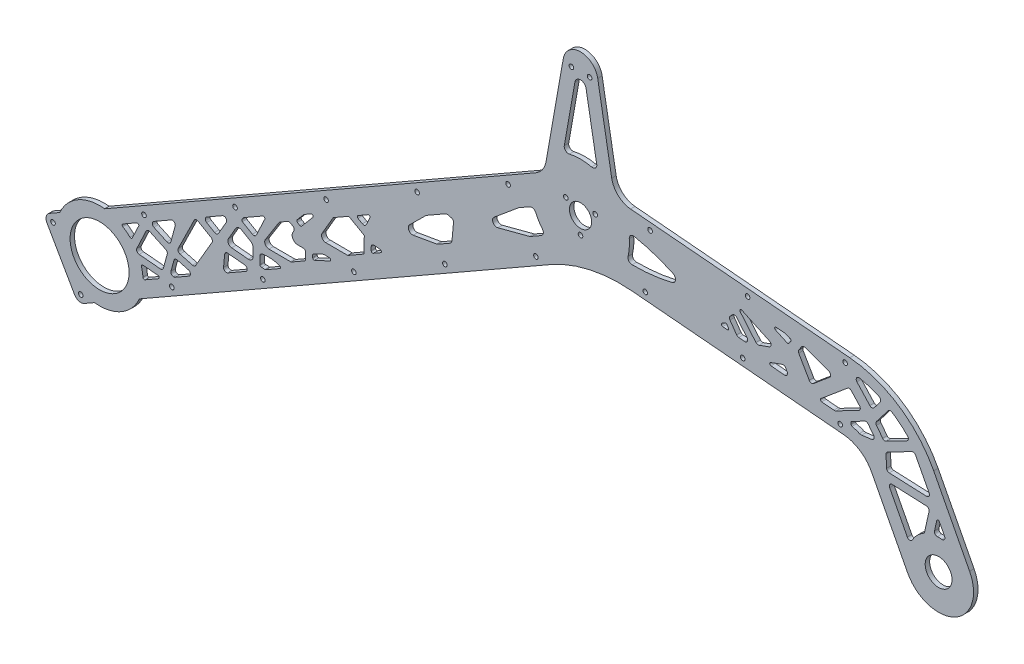
SolidWorks part; units mm, degrees
material "6061-T6 (SS)"
ref_plane "Front Plane" through (0, 0, 0) normal (0, 0, 1) x (1, 0, 0)
ref_plane "Top Plane" through (0, 0, 0) normal (0, 1, 0) x (1, 0, 0)
ref_plane "Right Plane" through (0, 0, 0) normal (1, 0, 0) x (0, 0, -1)
sketch "Reference Sketch" plane through (0, 0, 0) normal (0, 0, 1) x (1, 0, 0)
  line L0 (-343.92, -196.825) -> (0, 0) construction
  line L1 (-243.92, 103.175) -> (356.08, 103.175) construction
  line L2 (-243.92, 103.175) -> (-243.92, 0) construction
  line L3 (-243.92, 0) -> (356.08, 0) construction
  line L4 (356.08, 103.175) -> (356.08, 0) construction
  line L5 (0, 0) -> (256.08, -92.7116) construction
  line L6 (256.08, -92.7116) -> (56.08, -196.825) construction
  line L7 (256.08, -92.7116) -> (456.08, -196.825) construction
  line L8 (-343.92, -196.825) -> (56.08, -196.825) construction
  line L9 (56.08, -196.825) -> (456.08, -196.825) construction
  circle A1 centre (-343.92, -196.825) radius 100 construction
  circle A2 centre (56.08, -196.825) radius 100 construction
  circle A3 centre (456.08, -196.825) radius 100 construction
  circle A4 centre (-343.92, -196.825) radius 16.05 construction
  circle A5 centre (-343.92, -196.825) radius 28.55 construction
  circle A6 centre (-343.92, -196.825) radius 38.55 construction
  circle A7 centre (-343.92, -196.825) radius 33.55 construction
  point P13 (-343.92, -296.825)
  point P14 (556.08, -196.825)
  point P17 (-443.92, -196.825)
  dimension "D3" = 32.1
  dimension "D5" = 200
  dimension "D9" = 57.1
  dimension "D10" = 10
  dimension "D11" = 5
  dimension "D1" = 600
  dimension "D2" = 103.175
  dimension "D4" = 243.92
  dimension "D6" = 125
  dimension "D7" = 400
  dimension "D8" = 1000
sketch "Sketch2" plane through (0, 0, 0) normal (0, 0, 1) x (1, 0, 0)
  line L0 (-379.7168, -188.5069) -> (-32.0065, 10.4873)
  line L1 (-354.8814, -231.9028) -> (-21.5627, -41.1449)
  line L2 (-343.92, -196.825) -> (0, 0) construction
  line L3 (-184.3777, -76.7146) -> (-159.5423, -120.1104) construction
  line L4 (-24.685, 20.9013) -> (-12.3101, 91.0831)
  line L5 (12.3101, 91.0831) -> (22.322, 34.3028)
  line L6 (0, 98.4125) -> (0, 112.7) construction
  line L7 (-5.4848, 79.4125) -> (5.4848, 79.4125) construction
  line L8 (5.4848, 79.4125) -> (10.9697, 88.9125) construction
  line L9 (10.9697, 88.9125) -> (5.4848, 98.4125) construction
  line L10 (5.4848, 98.4125) -> (-5.4848, 98.4125) construction
  line L11 (-5.4848, 98.4125) -> (-10.9697, 88.9125) construction
  line L12 (-10.9697, 88.9125) -> (-5.4848, 79.4125) construction
  line L13 (-243.92, 103.175) -> (356.08, 103.175) construction
  line L14 (0, 88.9125) -> (0, 0) construction
  line L15 (35.7868, 21.9646) -> (192.5861, 8.2464)
  line L16 (252.5753, -31.8371) -> (278.2553, -81.1679)
  line L17 (233.9047, -104.2553) -> (208.2247, -54.9245)
  line L18 (36.8237, -28.3172) -> (188.2284, -41.5633)
  line L19 (0, 0) -> (192.5861, -16.8491) construction
  line L21 (-365.6311, -190.9191) -> (-338.0141, -175.1139) construction
  line L22 (-381.5729, -195.33) -> (-361.7045, -230.0467)
  line L23 (256.08, -92.7116) -> (56.08, -196.825) construction
  line L25 (-243.92, 0) -> (356.08, 0) construction
  circle A0 centre (0, 0) radius 7.9375
  circle A1 centre (-343.92, -196.825) radius 16.05
  arc A3 (-12.3101, 91.0831) -> (12.3101, 91.0831) centre (0, 88.9125) cw
  circle A4 centre (0, 88.9125) radius 6.5 construction
  circle A5 centre (-6.5, 88.9125) radius 1.65
  circle A6 centre (6.5, 88.9125) radius 1.65
  circle A7 centre (0, 88.9125) radius 9.5 construction
  arc A8 (252.5753, -31.8371) -> (192.5861, 8.2464) centre (186.0495, -66.4682) ccw
  circle A9 centre (256.08, -92.7116) radius 9.5885
  arc A10 (278.2553, -81.1679) -> (233.9047, -104.2553) centre (256.08, -92.7116) cw
  arc A11 (-21.5627, -41.1449) -> (36.8237, -28.3172) centre (28.1082, -127.9366) cw
  arc A12 (188.2284, -41.5633) -> (208.2247, -54.9245) centre (186.0495, -66.4682) cw
  arc A13 (22.322, 34.3028) -> (35.7868, 21.9646) centre (37.0941, 36.9075) ccw
  arc A14 (-32.0065, 10.4873) -> (-24.685, 20.9013) centre (-39.4572, 23.506) ccw
  circle A17 centre (-343.92, -196.825) radius 22.5 construction
  circle A18 centre (-365.6311, -190.9191) radius 1.65
  circle A19 centre (-338.0141, -175.1139) radius 1.65
  circle A20 centre (-322.2089, -202.7309) radius 1.65
  circle A21 centre (-349.8259, -218.5361) radius 1.65
  arc A27 (-379.7168, -188.5069) -> (-381.5729, -195.33) centre (-377.2333, -192.8465) ccw
  arc A28 (-361.7045, -230.0467) -> (-354.8814, -231.9028) centre (-357.3649, -227.5632) ccw
  circle A29 centre (-343.92, -196.825) radius 33.55 construction
  circle A32 centre (-343.92, -196.825) radius 38.55 construction
  point P16 (-171.96, -98.4125)
  point P64 (-343.92, -196.825)
  dimension "D1" = 15.875
  dimension "D2" = 32.1
  dimension "D3" = 45
  dimension "D5" = 13
  dimension "D6" = 3.3
  dimension "D7" = 6
  dimension "D12" = 50
  dimension "D14" = 100
  dimension "D16" = 15
  dimension "D17" = 5
  dimension "D18" = 25
  dimension "D19" = 3.3
  dimension "D15" = 4
  dimension "D20" = 19.177
  dimension "D4" = 50
  dimension "D8" = 19
  dimension "D9" = 14.2875
  dimension "D10" = 9.525
  dimension "D11" = 10
  dimension "D13" = 50
extrude "Base" add sketch "Sketch2" along normal blind 3.175
sketch "Sketch3" plane through (0, 0, 3.175) normal (0, 0, 1) x (1, 0, 0)
  line L0 (-343.92, -196.825) -> (0, 0) construction
  line L5 (0, 0) -> (197.3986, -17.2701) construction
  line L6 (192.5861, 8.2464) -> (35.7868, 21.9646) construction
  line L9 (36.8237, -28.3172) -> (188.2284, -41.5633) construction
  line L10 (-31.8958, -41.2976) -> (0, 0) construction
  line L11 (0, 0) -> (46.2693, -24.1244) construction
  circle A0 centre (-357.3649, -227.5632) radius 1.65
  circle A1 centre (-343.92, -196.825) radius 33.55 construction
  arc A2 (-361.7045, -230.0467) -> (-354.8814, -231.9028) centre (-357.3649, -227.5632) ccw construction
  circle A3 centre (-292.2711, -190.3101) radius 1.65
  circle A4 centre (-227.1773, -153.057) radius 1.65
  circle A5 centre (-162.0835, -115.8038) radius 1.65
  circle A6 centre (-96.9897, -78.5507) radius 1.65
  circle A7 centre (-31.8958, -41.2976) radius 1.65
  circle A8 centre (-312.1394, -155.5934) radius 1.65
  circle A9 centre (-377.2333, -192.8465) radius 1.65
  circle A10 centre (-247.0456, -118.3403) radius 1.65
  circle A11 centre (-181.9518, -81.0871) radius 1.65
  circle A12 centre (-116.858, -43.834) radius 1.65
  circle A13 centre (-51.7642, -6.5809) radius 1.65
  circle A14 centre (46.2693, -24.1244) radius 1.65
  circle A15 centre (116.0029, -30.2253) radius 1.65
  circle A16 centre (185.7366, -36.3262) radius 1.65
  circle A17 centre (189.2228, 3.5215) radius 1.65
  circle A18 centre (119.4892, 9.6224) radius 1.65
  circle A19 centre (49.7555, 15.7234) radius 1.65
  dimension "D1" = 3.3
  dimension "D2" = 6
  dimension "D3" = 5
  dimension "D5" = 3
  dimension "D4" = 75
  dimension "D6" = 70
extrude "Strut Holes" cut sketch "Sketch3" against normal through all
sketch "Sketch6" plane through (0, 0, 3.175) normal (0, 0, 1) x (1, 0, 0)
  line L0 (-315.2692, -197.7109) -> (-301.7593, -189.9792)
  line L1 (-354.8814, -231.9028) -> (-21.5627, -41.1449) construction
  line L2 (-289.845, -183.1607) -> (-279.9388, -177.4914)
  line L3 (-225.0683, -146.089) -> (-215.0659, -140.3647)
  line L4 (-202.4189, -105.5114) -> (-200.6862, -106.5205)
  line L5 (-330.4255, -170.6672) -> (-317.3783, -163.2003)
  line L6 (-32.0065, 10.4873) -> (-379.7168, -188.5069) construction
  line L7 (-315.9769, -164.4942) -> (-323.4022, -180.2613)
  line L8 (-325.3934, -181.4009) -> (-327.8261, -181.1787)
  line L9 (-302.165, -188.1154) -> (-317.5291, -186.7124)
  line L10 (-319.5204, -187.852) -> (-321.9207, -192.9489)
  line L11 (-295.5333, -171.6316) -> (-298.2962, -181.7883)
  line L12 (-300.4079, -183.2551) -> (-315.6625, -181.8621)
  line L13 (-317.2901, -179.0183) -> (-310.6415, -164.9005)
  line L14 (-307.9799, -163.9432) -> (-296.6111, -169.2972)
  line L15 (-280.4073, -173.8257) -> (-288.2923, -171.6808)
  line L16 (-290.7472, -173.0857) -> (-292.8686, -180.8843)
  line L17 (-292.7787, -149.122) -> (-305.2156, -156.2396)
  line L18 (-305.0743, -159.7848) -> (-295.766, -164.1685)
  line L19 (-292.984, -162.8841) -> (-289.8554, -151.3828)
  line L20 (-286.4122, -167.0105) -> (-277.4777, -169.4409)
  line L21 (-275.2245, -168.5176) -> (-263.487, -148.3649)
  line L22 (-264.2087, -145.6301) -> (-273.4911, -140.2238)
  line L23 (-276.2919, -141.0684) -> (-287.6814, -164.1971)
  line L24 (-267.3269, -134.556) -> (-255.9817, -128.0631)
  line L25 (-253.26, -130.8055) -> (-258.9575, -140.5878)
  line L26 (-261.6923, -141.3094) -> (-267.3401, -138.02)
  line L27 (-255.2613, -159.7424) -> (-254.4886, -151.2802)
  line L28 (-252.315, -149.4703) -> (-240.2297, -150.5739)
  line L29 (-292.2711, -190.3101) -> (-299.0066, -188.4038) construction
  line L30 (-252.2762, -161.6601) -> (-239.4181, -154.3014)
  line L31 (-246.5402, -131.1894) -> (-251.7948, -140.2114)
  line L32 (-249.4752, -144.7088) -> (-237.508, -145.8016)
  line L33 (-234.2352, -142.8254) -> (-234.2117, -136.6339)
  line L34 (-235.7018, -134.0302) -> (-242.4379, -130.1069)
  line L35 (-229.2226, -139.4963) -> (-229.2439, -145.1246)
  line L36 (-241.7536, -124.7193) -> (-234.6398, -128.8625)
  line L37 (-231.8238, -127.9864) -> (-225.7969, -115.1887)
  line L38 (-227.1983, -113.8948) -> (-240.4869, -121.4998)
  line L39 (-215.6688, -112.1749) -> (-225.38, -127.5855)
  line L40 (-222.8533, -132.1849) -> (-207.4544, -132.2434)
  line L41 (-206.4534, -131.9792) -> (-197.5057, -126.8584)
  line L42 (-196.4991, -125.1302) -> (-196.4845, -121.2849)
  line L43 (-198.4769, -119.2773) -> (-202.2607, -119.2629)
  line L44 (-205.6297, -113.1304) -> (-205.0269, -112.1739)
  line L45 (-205.7124, -109.3794) -> (-207.4618, -108.3605)
  line L46 (-209.4618, -108.3529) -> (-214.9702, -111.5053)
  line L47 (-223.2993, -137.1832) -> (-189.5978, -137.3112) construction
  line L48 (-199.4194, -106.3021) -> (-191.3609, -96.7721)
  line L49 (-192.6212, -95.2585) -> (-197.479, -98.0386)
  line L50 (-198.0128, -98.4831) -> (-202.6792, -104.0016)
  line L51 (-191.4798, -120.0542) -> (-191.4866, -121.8475)
  line L52 (-190.0674, -122.7592) -> (-179.2455, -117.7628)
  line L54 (-190.899, -119.1501) -> (-184.1308, -116.0253)
  line L55 (-183.2849, -115.8411) -> (-179.6609, -115.8549)
  line L56 (-166.4011, -107.9052) -> (-182.2049, -107.8452)
  line L57 (-184.7858, -103.3353) -> (-176.832, -89.6789)
  line L58 (-176.832, -89.6789) -> (-165.639, -83.2731)
  line L59 (-165.639, -83.2731) -> (-154.6405, -89.6789)
  line L60 (-154.6405, -89.6789) -> (-154.6842, -101.1996)
  line L61 (-154.6842, -101.1996) -> (-166.4011, -107.9052)
  line L62 (-176.832, -89.6789) -> (-166.4011, -107.9052) construction
  line L63 (-149.6667, -96.5998) -> (-149.6576, -94.1811)
  line L64 (-147.4757, -92.197) -> (-143.2847, -92.5797)
  line L65 (-142.8789, -94.4434) -> (-148.17, -97.4715)
  line L66 (-159.1247, -79.5451) -> (-152.014, -75.4756)
  line L67 (-150.6126, -76.7696) -> (-153.1821, -82.2258)
  line L68 (-155.9981, -83.102) -> (-159.1313, -81.2771)
  line L69 (-154.1121, -84.2004) -> (-149.6493, -91.9985) construction
  line L70 (-90.8199, -49.6985) -> (-91.8964, -61.4879)
  line L71 (-93.3939, -63.8188) -> (-101.9943, -68.7409)
  line L72 (-102.9747, -69.0935) -> (-119.6299, -71.9651)
  line L73 (-122.2529, -66.8794) -> (-110.6811, -55.3952)
  line L74 (-110.058, -54.9208) -> (-96.7247, -47.2901)
  line L75 (-94.4471, -46.9991) -> (-92.2866, -47.5868)
  line L76 (-102.4534, -69.0036) -> (-110.4008, -55.117) construction
  line L78 (-28.0968, -26.4494) -> (-35.8254, -30.8725)
  line L79 (-36.5501, -31.1694) -> (-59.134, -37.129)
  line L80 (-61.819, -31.9228) -> (-44.3172, -17.3499)
  line L81 (-43.8877, -17.0516) -> (-36.2746, -12.6946)
  line L82 (-44.1155, -17.182) -> (-36.1682, -31.0687) construction
  line L83 (-11.5997, 37.5245) -> (-3.9861, 80.7029)
  line L84 (3.9861, 80.7029) -> (11.5997, 37.5245)
  line L85 (22.322, 34.3028) -> (12.3101, 91.0831) construction
  line L86 (-12.3101, 91.0831) -> (-24.685, 20.9013) construction
  line L87 (192.5861, 8.2464) -> (35.7868, 21.9646) construction
  line L88 (36.8237, -28.3172) -> (188.2284, -41.5633) construction
  line L89 (-227.1773, -153.057) -> (-233.9128, -151.1507) construction
  line L90 (246.076, -72.9136) -> (249.254, -58.5784)
  line L91 (247.3887, -56.1475) -> (222.9622, -55.081)
  line L92 (221.1009, -58.0026) -> (233.7353, -82.273)
  line L93 (208.2247, -54.9245) -> (233.9047, -104.2553) construction
  line L94 (253.1337, -68.7997) -> (254.752, -61.5)
  line L95 (256.6153, -61.2547) -> (260.3456, -68.4206)
  line L96 (278.2553, -81.1679) -> (252.5753, -31.8371) construction
  line L97 (249.3108, -47.2228) -> (239.5975, -28.5637)
  line L98 (236.9, -27.7132) -> (219.5656, -36.7369)
  line L99 (218.491, -38.5982) -> (218.8608, -47.0688)
  line L100 (220.7717, -48.9796) -> (247.4495, -50.1444)
  line L101 (233.4135, -22.7639) -> (218.6181, -30.4658)
  line L102 (216.1079, -29.9093) -> (211.6718, -24.1281)
  line L103 (211.6718, -21.693) -> (220.0072, -10.8302)
  line L104 (209.6166, -31.3057) -> (205.7463, -26.2618)
  line L105 (203.2361, -25.7053) -> (194.0101, -30.5081)
  line L106 (193.4718, -31.3951) -> (193.4718, -32.4967)
  line L107 (201.069, -35.4569) -> (208.2909, -34.5061)
  line L108 (214.3031, -8.4078) -> (209.9577, -14.0708)
  line L109 (197.6887, -4.156) -> (206.8964, -14.2045)
  line L110 (193.6814, -11.6243) -> (199.5455, -18.0239)
  line L111 (198.9945, -21.1491) -> (182.8075, -29.5754)
  line L112 (181.1608, -29.903) -> (172.4826, -29.1438)
  line L113 (171.927, -27.3815) -> (190.9213, -11.4434)
  line L114 (178.1992, -11.0225) -> (166.5918, -20.7623)
  line L115 (163.5742, -20.2302) -> (156.048, -7.1944)
  line L116 (156.1417, -5.0472) -> (158.1885, -2.1242)
  line L117 (160.5108, -1.3919) -> (177.5977, -7.611)
  line L118 (146.6448, -20.9077) -> (147.747, -22.8167)
  line L119 (145.8406, -25.8091) -> (136.23, -24.9682)
  line L120 (135.9751, -23.0324) -> (144.2287, -20.0283)
  line L121 (134.9743, -13.819) -> (127.6718, -16.4769)
  line L122 (125.4557, -15.8831) -> (114.1985, -2.4673)
  line L123 (115.3872, -0.9182) -> (135.1355, -10.127)
  line L124 (139.4306, -1.096) -> (147.8318, -5.0136)
  line L125 (149.0736, -4.6809) -> (150.4259, -2.7496)
  line L126 (149.9488, -1.2363) -> (146.0985, 0.1651)
  line L127 (145.3339, 0.3346) -> (139.9404, 0.8065)
  line L128 (111.6605, -7.2212) -> (119.0455, -16.0223)
  line L129 (117.3391, -19.3002) -> (113.1162, -18.9308)
  line L130 (111.6522, -18.0855) -> (106.8775, -11.2665)
  line L131 (107.1016, -8.7052) -> (108.7142, -7.0926)
  line L132 (104.7039, -15.1361) -> (105.7554, -16.6377)
  line L133 (104.8491, -18.2075) -> (101.6773, -17.93)
  line L134 (101.2644, -16.0678) -> (103.3847, -14.8436)
  arc A0 (-317.584, -197.4764) -> (-320.5599, -195.9279) centre (-322.2089, -202.7309) ccw
  arc A1 (-291.1568, -183.3993) -> (-291.2348, -183.3872) centre (-292.2711, -190.3101) ccw
  arc A2 (-225.7665, -146.2006) -> (-228.1106, -146.1195) centre (-227.1773, -153.057) ccw
  arc A4 (-322.0747, -194.2209) -> (-322.0953, -194.053) centre (-343.92, -196.825) ccw
  arc A5 (-331.3132, -177.1382) -> (-331.3392, -173.0054) centre (-338.0141, -175.1139) ccw
  arc A6 (-329.0005, -180.6569) -> (-330.6088, -179.309) centre (-343.92, -196.825) ccw
  arc A8 (-227.5555, -137.5318) -> (-215.2363, -138.5515) centre (-223.3943, -162.1831) cw
  arc A9 (-241.9747, -123.1658) -> (-241.1717, -122.1478) centre (-247.0456, -118.3403) ccw
  arc A10 (-32.0383, -14.0906) -> (-27.2511, -21.9631) centre (0, 0) ccw
  arc A11 (-251.7948, -140.2114) -> (-249.4752, -144.7088) centre (-249.2024, -141.7213) ccw
  arc A12 (-225.38, -127.5855) -> (-222.8533, -132.1849) centre (-222.8419, -129.1849) ccw
  arc A13 (-182.2049, -107.8452) -> (-184.7858, -103.3353) centre (-182.1935, -104.8452) cw
  arc A14 (-119.6299, -71.9651) -> (-122.2529, -66.8794) centre (-120.1396, -69.0087) cw
  arc A15 (-59.134, -37.129) -> (-61.819, -31.9228) centre (-59.8994, -34.2283) cw
  arc A16 (-7.9627, 34.0822) -> (7.9627, 34.0822) centre (0, 0) cw
  arc A17 (-3.9861, 80.7029) -> (3.9861, 80.7029) centre (0, 80) cw
  arc A18 (34.8636, 3.0867) -> (34.0029, -8.2948) centre (0, 0) cw
  arc A19 (38.4335, 6.2944) -> (66.0977, -2.7713) centre (15.1723, -111.4295) cw
  arc A20 (66.0977, -2.7713) -> (65.4856, -8.7407) centre (64.749, -5.6491) cw
  arc A21 (36.898, -12.0057) -> (65.4856, -8.7407) centre (37.6733, 107.9918) ccw
  arc A22 (245.141, -74.2025) -> (237.26, -82.3165) centre (256.08, -92.7116) ccw
  arc A23 (258.3595, -71.3328) -> (255.1708, -71.2308) centre (256.08, -92.7116) ccw
  arc A24 (222.6875, -10.3732) -> (233.9189, -19.5905) centre (186.0495, -66.4682) cw
  arc A25 (252.5753, -31.8371) -> (192.5861, 8.2464) centre (186.0495, -66.4682) ccw construction
  arc A26 (194.2312, -33.4673) -> (199.4914, -35.2382) centre (186.0495, -66.4682) cw
  arc A27 (208.2247, -54.9245) -> (188.2284, -41.5633) centre (186.0495, -66.4682) ccw construction
  arc A28 (213.5369, -5.3663) -> (199.5667, -0.8459) centre (186.0495, -66.4682) ccw
  arc A29 (218.8608, -47.0688) -> (220.7717, -48.9796) centre (220.8589, -46.9815) ccw
  arc A30 (239.5975, -28.5637) -> (236.9, -27.7132) centre (237.8235, -29.4872) ccw
  arc A31 (219.5656, -36.7369) -> (218.491, -38.5982) centre (220.4891, -38.5109) ccw
  arc A32 (127.6718, -16.4769) -> (125.4557, -15.8831) centre (126.9878, -14.5975) cw
  arc A33 (-240.4869, -121.4998) -> (-241.1717, -122.1478) centre (-239.4934, -123.2356) ccw
  arc A34 (-234.6398, -128.8625) -> (-231.8238, -127.9864) centre (-233.6332, -127.1343) ccw
  arc A35 (-229.2226, -139.4963) -> (-227.5555, -137.5318) centre (-227.2226, -139.5039) cw
  arc A36 (-315.2692, -197.7109) -> (-317.584, -197.4764) centre (-316.2626, -195.9751) cw
  arc A37 (-322.0747, -194.2209) -> (-320.5599, -195.9279) centre (-320.0887, -193.9842) ccw
  arc A38 (-321.9207, -192.9489) -> (-322.0953, -194.053) centre (-320.1113, -193.801) ccw
  arc A39 (-317.5291, -186.7124) -> (-319.5204, -187.852) centre (-317.711, -188.7042) ccw
  arc A40 (-323.4022, -180.2613) -> (-325.3934, -181.4009) centre (-325.2116, -179.4092) cw
  arc A41 (-327.8261, -181.1787) -> (-329.0005, -180.6569) centre (-327.6442, -179.187) cw
  arc A42 (-331.3132, -177.1382) -> (-330.6088, -179.309) centre (-329.3986, -177.7166) ccw
  arc A43 (-330.4255, -170.6672) -> (-331.3392, -173.0054) centre (-329.4321, -172.403) ccw
  arc A44 (-315.6625, -181.8621) -> (-317.2901, -179.0183) centre (-315.4807, -179.8704) cw
  arc A45 (-298.2962, -181.7883) -> (-300.4079, -183.2551) centre (-300.226, -181.2634) cw
  arc A46 (-289.845, -183.1607) -> (-291.1568, -183.3993) centre (-290.8384, -181.4248) cw
  arc A47 (-292.8686, -180.8843) -> (-291.2348, -183.3872) centre (-290.9387, -181.4092) ccw
  arc A48 (-280.4073, -173.8257) -> (-279.9388, -177.4914) centre (-280.9322, -175.7556) cw
  arc A49 (-288.2923, -171.6808) -> (-290.7472, -173.0857) centre (-288.8173, -173.6107) ccw
  arc A50 (-295.5333, -171.6316) -> (-296.6111, -169.2972) centre (-297.4632, -171.1066) ccw
  arc A51 (-310.6415, -164.9005) -> (-307.9799, -163.9432) centre (-308.8321, -165.7526) cw
  arc A52 (-305.2156, -156.2396) -> (-305.0743, -159.7848) centre (-304.2222, -157.9754) ccw
  arc A53 (-292.7787, -149.122) -> (-289.8554, -151.3828) centre (-291.7853, -150.8578) cw
  arc A54 (-295.766, -164.1685) -> (-292.984, -162.8841) centre (-294.9139, -162.3591) ccw
  arc A55 (-286.4122, -167.0105) -> (-287.6814, -164.1971) centre (-285.8872, -165.0807) cw
  arc A56 (-277.4777, -169.4409) -> (-275.2245, -168.5176) centre (-276.9527, -167.511) ccw
  arc A57 (-263.487, -148.3649) -> (-264.2087, -145.6301) centre (-265.2153, -147.3583) ccw
  arc A58 (-273.4911, -140.2238) -> (-276.2919, -141.0684) centre (-274.4977, -141.952) ccw
  arc A59 (-267.3269, -134.556) -> (-267.3401, -138.02) centre (-266.3335, -136.2918) ccw
  arc A60 (-258.9575, -140.5878) -> (-261.6923, -141.3094) centre (-260.6857, -139.5812) cw
  arc A61 (-254.4886, -151.2802) -> (-252.315, -149.4703) centre (-252.4969, -151.462) cw
  arc A62 (-255.2613, -159.7424) -> (-252.2762, -161.6601) centre (-253.2696, -159.9243) ccw
  arc A63 (-239.4181, -154.3014) -> (-240.2297, -150.5739) centre (-240.4115, -152.5656) ccw
  arc A64 (-255.9817, -128.0631) -> (-253.26, -130.8055) centre (-254.9883, -129.7989) cw
  arc A65 (-207.4544, -132.2434) -> (-206.4534, -131.9792) centre (-207.4468, -130.2434) ccw
  arc A66 (-214.9702, -111.5053) -> (-215.6688, -112.1749) centre (-213.9767, -113.2412) ccw
  arc A67 (-207.4618, -108.3605) -> (-209.4618, -108.3529) centre (-208.4684, -110.0887) ccw
  arc A68 (-205.0269, -112.1739) -> (-205.7124, -109.3794) centre (-206.719, -111.1076) ccw
  arc A69 (-202.2607, -119.2629) -> (-205.6297, -113.1304) centre (-202.2456, -115.263) cw
  arc A70 (-196.4845, -121.2849) -> (-198.4769, -119.2773) centre (-198.4845, -121.2773) ccw
  arc A71 (-197.5057, -126.8584) -> (-196.4991, -125.1302) centre (-198.4991, -125.1226) ccw
  arc A72 (-184.1308, -116.0253) -> (-183.2849, -115.8411) centre (-183.2925, -117.8411) cw
  arc A73 (-197.479, -98.0386) -> (-198.0128, -98.4831) centre (-196.4856, -99.7744) ccw
  arc A74 (-149.6576, -94.1811) -> (-147.4757, -92.197) centre (-147.6576, -94.1887) cw
  arc A75 (-153.1821, -82.2258) -> (-155.9981, -83.102) centre (-154.9915, -81.3737) cw
  arc A76 (-90.8199, -49.6985) -> (-92.2866, -47.5868) centre (-92.8116, -49.5167) ccw
  arc A77 (111.6605, -7.2212) -> (108.7142, -7.0926) centre (110.1284, -8.5068) ccw
  arc A78 (106.8775, -11.2665) -> (107.1016, -8.7052) centre (108.5158, -10.1194) cw
  arc A79 (113.1162, -18.9308) -> (111.6522, -18.0855) centre (113.2905, -16.9384) cw
  arc A80 (119.0455, -16.0223) -> (117.3391, -19.3002) centre (117.5134, -17.3078) cw
  arc A81 (134.9743, -13.819) -> (135.1355, -10.127) centre (134.2903, -11.9396) ccw
  arc A82 (146.6448, -20.9077) -> (144.2287, -20.0283) centre (144.9128, -21.9077) ccw
  arc A83 (147.747, -22.8167) -> (145.8406, -25.8091) centre (146.0149, -23.8167) cw
  arc A84 (156.048, -7.1944) -> (156.1417, -5.0472) centre (157.78, -6.1944) cw
  arc A85 (158.1885, -2.1242) -> (160.5108, -1.3919) centre (159.8268, -3.2713) cw
  arc A86 (178.1992, -11.0225) -> (177.5977, -7.611) centre (176.9136, -9.4904) ccw
  arc A87 (166.5918, -20.7623) -> (163.5742, -20.2302) centre (165.3062, -19.2302) cw
  arc A88 (193.6814, -11.6243) -> (190.9213, -11.4434) centre (192.2068, -12.9755) ccw
  arc A89 (199.5455, -18.0239) -> (198.9945, -21.1491) centre (198.071, -19.375) cw
  arc A90 (209.9577, -14.0708) -> (206.8964, -14.2045) centre (208.371, -12.8533) cw
  arc A91 (213.5369, -5.3663) -> (214.3031, -8.4078) centre (212.7164, -7.1903) cw
  arc A92 (233.9189, -19.5905) -> (233.4135, -22.7639) centre (232.49, -20.9899) cw
  arc A93 (222.6875, -10.3732) -> (220.0072, -10.8302) centre (221.5939, -12.0477) ccw
  arc A94 (211.6718, -24.1281) -> (211.6718, -21.693) centre (213.2585, -22.9105) cw
  arc A95 (218.6181, -30.4658) -> (216.1079, -29.9093) centre (217.6946, -28.6918) cw
  arc A96 (205.7463, -26.2618) -> (203.2361, -25.7053) centre (204.1595, -27.4793) ccw
  arc A97 (209.6166, -31.3057) -> (208.2909, -34.5061) centre (208.0299, -32.5232) cw
  arc A98 (246.076, -72.9136) -> (245.141, -74.2025) centre (244.1234, -72.4807) cw
  arc A99 (249.254, -58.5784) -> (247.3887, -56.1475) centre (247.3014, -58.1456) ccw
  arc A100 (222.9622, -55.081) -> (221.1009, -58.0026) centre (222.8749, -57.0791) ccw
  arc A101 (233.7353, -82.273) -> (237.26, -82.3165) centre (235.5093, -81.3495) ccw
  arc A102 (260.3456, -68.4206) -> (258.3595, -71.3328) centre (258.5716, -69.344) cw
  arc A103 (253.1337, -68.7997) -> (255.1708, -71.2308) centre (255.0863, -69.2326) ccw
  arc A104 (249.3108, -47.2228) -> (247.4495, -50.1444) centre (247.5367, -48.1463) cw
  arc A105 (199.5667, -0.8459) -> (197.6887, -4.156) centre (199.1632, -2.8048) ccw
  arc A106 (-215.2363, -138.5515) -> (-215.0659, -140.3647) centre (-215.5626, -139.4968) cw
  arc A107 (-301.7593, -189.9792) -> (-302.165, -188.1154) centre (-302.256, -189.1113) ccw
  arc A108 (-317.3783, -163.2003) -> (-315.9769, -164.4942) centre (-316.8815, -164.0682) cw
  arc A109 (-225.7969, -115.1887) -> (-227.1983, -113.8948) centre (-226.7016, -114.7627) ccw
  arc A110 (-241.7536, -124.7193) -> (-241.9747, -123.1658) centre (-241.2503, -123.8551) cw
  arc A111 (-225.7665, -146.2006) -> (-225.0683, -146.089) centre (-225.565, -145.2211) ccw
  arc A112 (-229.2439, -145.1246) -> (-228.1106, -146.1195) centre (-228.2439, -145.1284) ccw
  arc A113 (-202.4189, -105.5114) -> (-202.6792, -104.0016) centre (-201.9156, -104.6473) cw
  arc A114 (-200.6862, -106.5205) -> (-199.4194, -106.3021) centre (-200.183, -105.6564) ccw
  arc A115 (-191.4798, -120.0542) -> (-190.899, -119.1501) centre (-190.4798, -120.058) cw
  arc A116 (-191.4866, -121.8475) -> (-190.0674, -122.7592) centre (-190.4866, -121.8513) ccw
  arc A117 (-191.3609, -96.7721) -> (-192.6212, -95.2585) centre (-192.1245, -96.1264) ccw
  arc A118 (-179.2455, -117.7628) -> (-179.6609, -115.8549) centre (-179.6647, -116.8549) ccw
  arc A119 (-152.014, -75.4756) -> (-150.6126, -76.7696) centre (-151.5173, -76.3435) cw
  arc A120 (-159.1247, -79.5451) -> (-159.1313, -81.2771) centre (-158.628, -80.413) ccw
  arc A121 (-149.6667, -96.5998) -> (-148.17, -97.4715) centre (-148.6667, -96.6036) ccw
  arc A122 (-143.2847, -92.5797) -> (-142.8789, -94.4434) centre (-143.3756, -93.5755) cw
  arc A123 (101.6773, -17.93) -> (101.2644, -16.0678) centre (101.7644, -16.9338) cw
  arc A124 (104.7039, -15.1361) -> (103.3847, -14.8436) centre (103.8847, -15.7096) ccw
  arc A125 (105.7554, -16.6377) -> (104.8491, -18.2075) centre (104.9362, -17.2113) cw
  arc A126 (114.1985, -2.4673) -> (115.3872, -0.9182) centre (114.9646, -1.8245) cw
  arc A127 (136.23, -24.9682) -> (135.9751, -23.0324) centre (136.3171, -23.972) cw
  arc A128 (139.4306, -1.096) -> (139.9404, 0.8065) centre (139.8532, -0.1897) cw
  arc A129 (172.4826, -29.1438) -> (171.927, -27.3815) centre (172.5698, -28.1476) cw
  arc A130 (194.0101, -30.5081) -> (193.4718, -31.3951) centre (194.4718, -31.3951) ccw
  arc A131 (193.4718, -32.4967) -> (194.2312, -33.4673) centre (194.4718, -32.4967) ccw
  arc A132 (254.752, -61.5) -> (256.6153, -61.2547) centre (255.7283, -61.7164) cw
  arc A133 (146.0985, 0.1651) -> (145.3339, 0.3346) centre (145.0724, -2.654) ccw
  arc A134 (199.4914, -35.2382) -> (201.069, -35.4569) centre (200.6774, -32.4826) ccw
  arc A135 (182.8075, -29.5754) -> (181.1608, -29.903) centre (181.4223, -26.9144) cw
  arc A136 (-7.9627, 34.0822) -> (-11.5997, 37.5245) centre (-8.6452, 37.0035) cw
  arc A137 (7.9627, 34.0822) -> (11.5997, 37.5245) centre (8.6452, 37.0035) ccw
  arc A138 (34.8636, 3.0867) -> (38.4335, 6.2944) centre (37.8519, 3.3513) cw
  arc A139 (34.0029, -8.2948) -> (36.898, -12.0057) centre (36.9174, -9.0058) ccw
  arc A140 (-35.8254, -30.8725) -> (-36.5501, -31.1694) centre (-37.3155, -28.2687) cw
  arc A141 (-44.3172, -17.3499) -> (-43.8877, -17.0516) centre (-42.3976, -19.6554) cw
  arc A142 (-32.0383, -14.0906) -> (-36.2746, -12.6946) centre (-34.7845, -15.2984) ccw
  arc A143 (-27.2511, -21.9631) -> (-28.0968, -26.4494) centre (-29.5869, -23.8456) cw
  arc A144 (-96.7247, -47.2901) -> (-94.4471, -46.9991) centre (-95.2346, -49.8939) cw
  arc A145 (-91.8964, -61.4879) -> (-93.3939, -63.8188) centre (-94.884, -61.2151) cw
  arc A146 (-110.6811, -55.3952) -> (-110.058, -54.9208) centre (-108.5679, -57.5245) cw
  arc A147 (-101.9943, -68.7409) -> (-102.9747, -69.0935) centre (-103.4845, -66.1371) cw
  arc A148 (-246.5402, -131.1894) -> (-242.4379, -130.1069) centre (-243.9478, -132.6992) cw
  arc A149 (-234.2117, -136.6339) -> (-235.7018, -134.0302) centre (-237.2117, -136.6225) ccw
  arc A150 (-237.508, -145.8016) -> (-234.2352, -142.8254) centre (-237.2352, -142.8141) ccw
  arc A151 (150.4259, -2.7496) -> (149.9488, -1.2363) centre (149.6067, -2.176) ccw
  arc A152 (147.8318, -5.0136) -> (149.0736, -4.6809) centre (148.2544, -4.1073) ccw
  point P98 (-116.858, -43.834)
  point P110 (-254.1648, -144.2806)
  point P113 (-228.2654, -132.1643)
  point P143 (34.9003, -2.6394)
  point P203 (218.9408, -48.8997)
  point P206 (238.674, -26.7897)
  point P211 (126.3559, -16.9559)
  point P214 (-240.9361, -121.7569)
  point P217 (-232.7537, -129.961)
  point P220 (-229.2164, -137.8704)
  point P229 (-318.9237, -186.5851)
  point P232 (-323.9988, -181.5282)
  point P235 (-328.5183, -181.1155)
  point P240 (-331.9839, -171.5591)
  point P247 (-290.5028, -183.5371)
  point P252 (-275.7482, -175.0931)
  point P255 (-290.2222, -171.1558)
  point P262 (-308.5502, -158.1479)
  point P265 (-288.588, -146.7237)
  point P268 (-293.6097, -165.184)
  point P271 (-288.7533, -166.3737)
  point P278 (-275.3444, -139.1443)
  point P281 (-270.3335, -136.2766)
  point P288 (-255.6107, -163.5684)
  point P294 (-249.5035, -124.3556)
  point P297 (-206.9185, -132.2454)
  point P300 (-215.403, -111.753)
  point P303 (-208.4596, -107.7794)
  point P308 (-209.4769, -119.2355)
  point P311 (-196.4769, -119.2849)
  point P314 (-196.5035, -126.2849)
  point P329 (110.2575, -5.5492)
  point P334 (112.1872, -18.8495)
  point P337 (122.1491, -19.721)
  point P340 (139.5116, -12.1676)
  point P345 (149.6679, -26.1439)
  point P350 (159.0687, -0.8671)
  point P353 (180.8529, -8.7958)
  point P356 (164.7659, -22.2944)
  point P363 (208.5067, -15.9618)
  point P366 (215.8118, -6.4415)
  point P369 (235.7568, -21.544)
  point P374 (210.7376, -22.9105)
  point P377 (217.1296, -31.2407)
  point P380 (204.7246, -24.9304)
  point P383 (211.7254, -34.054)
  point P390 (219.5014, -54.9299)
  point P393 (235.6626, -85.9753)
  point P396 (262.2729, -72.1228)
  point P401 (250.9103, -50.2955)
  point P406 (-213.2581, -139.3301)
  point P412 (-314.6256, -161.6249)
  point P415 (-224.4456, -112.3194)
  point P420 (-225.4089, -146.284)
  point P423 (-229.2487, -146.3704)
  point P426 (-203.4487, -104.9116)
  point P431 (-191.4774, -119.4171)
  point P434 (-191.4925, -123.4171)
  point P437 (-187.699, -92.4415)
  point P440 (-175.1502, -115.872)
  point P447 (-149.6733, -98.3319)
  point P450 (-140.1262, -92.8681)
  point P453 (98.5177, -17.6536)
  point P458 (106.9854, -18.3944)
  point P463 (131.7364, -24.5751)
  point P468 (170.0776, -28.9333)
  point P471 (193.4718, -30.7883)
  point P474 (193.4718, -33.2883)
  point P477 (255.3467, -58.8176)
  point P484 (182.0319, -29.9792)
  point P491 (34.2849, 7.0387)
  point P494 (32.91, -11.9136)
  point P505 (-24.8853, -24.6115)
  point P508 (-95.6462, -46.6729)
  point P511 (-92.0384, -63.0431)
  point P524 (-234.2477, -146.0993)
  point P527 (151.1734, -1.682)
  point P530 (148.5923, -5.3682)
  dimension "D1" = 14
  dimension "D2" = 10
  dimension "D3" = 2
  dimension "D5" = 22
  dimension "D6" = 9
  dimension "D12" = 5
  dimension "D19" = 7
  dimension "D31" = 7
  dimension "D40" = 25
  dimension "D44" = 19
  dimension "D62" = 5
  dimension "D92" = 35
  dimension "D96" = 3
  dimension "D97" = 10
  dimension "D100" = 15
  dimension "D104" = 30
  dimension "D105" = 120
  dimension "D107" = 43
  dimension "D116" = 65
  dimension "D117" = 8
  dimension "D127" = 9
  dimension "D128" = 6
  dimension "D171" = 2
  dimension "D172" = 1
  dimension "D173" = 3
  dimension "D174" = 1
  dimension "D175" = 4
  dimension "D7" = 35
  dimension "D8" = 35
  dimension "D9" = 20
  dimension "D10" = 22
  dimension "D11" = 20
  dimension "D13" = 5
  dimension "D14" = 45
  dimension "D15" = 45
  dimension "D16" = 17
  dimension "D17" = 15
  dimension "D18" = 5
  dimension "D20" = 55
  dimension "D21" = 5
  dimension "D22" = 45
  dimension "D23" = 23
  dimension "D24" = 34
  dimension "D25" = 60
  dimension "D26" = 5
  dimension "D27" = 5
  dimension "D28" = 5
  dimension "D29" = 30
  dimension "D30" = 24
  dimension "D32" = 55
  dimension "D33" = 35
  dimension "D34" = 25
  dimension "D35" = 5
  dimension "D36" = 6
  dimension "D37" = 60
  dimension "D38" = 5
  dimension "D39" = 20
  dimension "D41" = 11
  dimension "D42" = 35
  dimension "D43" = 60
  dimension "D45" = 19.5
  dimension "D46" = 5
  dimension "D47" = 5
  dimension "D48" = 30
  dimension "D49" = 5
  dimension "D50" = 14
  dimension "D51" = 13
  dimension "D52" = 8.5
  dimension "D53" = 60
  dimension "D54" = 12
  dimension "D55" = 7
  dimension "D56" = 22
  dimension "D57" = 28
  dimension "D58" = 60
  dimension "D59" = 15
  dimension "D60" = 8
  dimension "D61" = 13
  dimension "D63" = 12
  dimension "D64" = 20
  dimension "D65" = 5
  dimension "D66" = 65
  dimension "D67" = 25
  dimension "2" = 18
  dimension "D68" = 8
  dimension "D69" = 4
  dimension "D70" = 14
  dimension "D71" = 15
  dimension "D72" = 13.5
  dimension "D73" = 60
  dimension "D74" = 60
  dimension "D75" = 8
  dimension "D76" = 5
  dimension "D77" = 35
  dimension "D78" = 0.5076
  dimension "D79" = 5
  dimension "D80" = 11
  dimension "D81" = 35
  dimension "D82" = 16
  dimension "D83" = 18
  dimension "D84" = 55
  dimension "D85" = 45
  dimension "D86" = 20
  dimension "D87" = 15
  dimension "D88" = 12
  dimension "D89" = 17
  dimension "D90" = 16
  dimension "D91" = 18
  dimension "D93" = 15
  dimension "D94" = 10
  dimension "D95" = 13
  dimension "D98" = 10
  dimension "D99" = 80
  dimension "D101" = 16
  dimension "D102" = 22
  dimension "D103" = 22
  dimension "D106" = 7
  dimension "D108" = 10
  dimension "D109" = 40
  dimension "D110" = 10
  dimension "D111" = 6
  dimension "D112" = 60
  dimension "D113" = 35
  dimension "D114" = 15
  dimension "D115" = 6
  dimension "D118" = 26.5
  dimension "D119" = 6
  dimension "D120" = 85
  dimension "D121" = 85
  dimension "D122" = 32
  dimension "D123" = 21
  dimension "D124" = 80
  dimension "D125" = 75
  dimension "D126" = 6
  dimension "D129" = 10.5
  dimension "D130" = 80
  dimension "D131" = 12
  dimension "D132" = 8
  dimension "D133" = 6
  dimension "D134" = 2.5
  dimension "D135" = 100
  dimension "D136" = 11.5
  dimension "D137" = 60
  dimension "D138" = 11
  dimension "D139" = 45
  dimension "D140" = 12
  dimension "D141" = 8.5
  dimension "D142" = 12
  dimension "D143" = 18
  dimension "D144" = 80
  dimension "D145" = 21
  dimension "D146" = 60
  dimension "D147" = 60
  dimension "D148" = 15
  dimension "D149" = 12
  dimension "D150" = 18
  dimension "D151" = 25
  dimension "D152" = 9
  dimension "D153" = 12
  dimension "D154" = 6
  dimension "D155" = 15
  dimension "D156" = 20
  dimension "D157" = 10
  dimension "D158" = 13.5
  dimension "D159" = 4.5
  dimension "D160" = 45
  dimension "D161" = 14
  dimension "D162" = 5
  dimension "D163" = 10
  dimension "D164" = 16
  dimension "D165" = 50
  dimension "D166" = 18.5
  dimension "D167" = 50
  dimension "D168" = 4
  dimension "D169" = 8.5
  dimension "D170" = 35
extrude "Lightening Holes" cut sketch "Sketch6" against normal through all
sketch "Sketch7" plane through (0, 0, 3.175) normal (0, 0, 1) x (1, 0, 0)
  circle A0 centre (-343.92, -196.825) radius 16.05 construction
  circle A28 centre (-343.92, -196.825) radius 31.1
  circle A29 centre (-343.92, -196.825) radius 21.1
  dimension "D1" = 42.2
  dimension "D2" = 10
extrude "Inner Mod Extrusion" add sketch "Sketch7" against normal up to surface (3.175 mm away) up to face at (-260.7262, -135.4767, 0)
extrude "Inner Mod Cut" cut sketch "Sketch7<2>" against normal through all contours A29 region at (-343.92, -196.825, 3.175)
sketch "Sketch7<2>" plane through (0, 0, 3.175) normal (0, 0, 1) x (1, 0, 0) same geometry as "Sketch7"
sketch "Sketch8" plane through (0, 0, 3.175) normal (0, 0, 1) x (1, 0, 0)
  circle A0 centre (-10.5, 6.0622) radius 1.65
  circle A1 centre (10.5, 6.0622) radius 1.65
  circle A2 centre (0, -12.1244) radius 1.65
  point P0 (0, 0)
  point P1 (0, 0)
  point P14 (0, 0)
  dimension "D2" = 3.3
  dimension "D1" = 21
  dimension "D3" = 3
extrude "Cut-Extrude1" cut sketch "Sketch8" against normal through all
fillet "Fillet1" radius 1 4 edges at (-328.7213, -169.6918, 1.5875) (-321.2009, -175.587, 1.5875) (-312.8242, -196.3117, 1.5875) (-314.4137, -186.9969, 1.5875)
